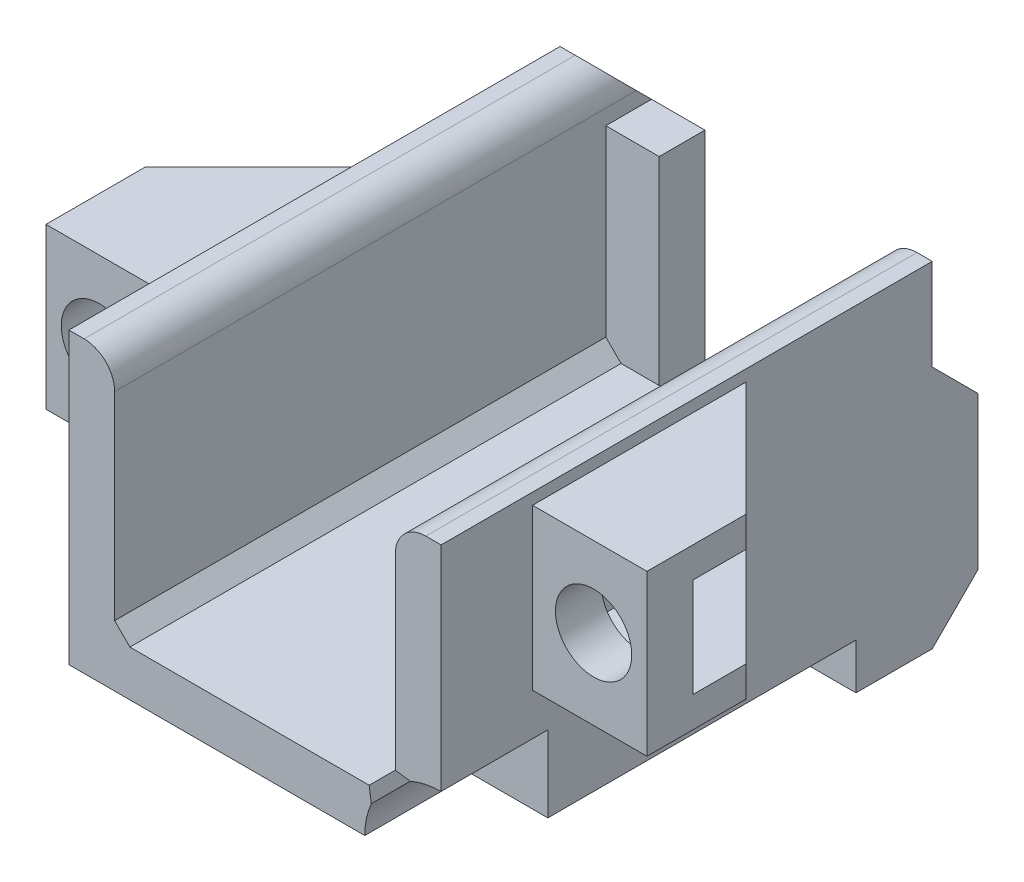
SolidWorks part; units mm, degrees
ref_plane "Front Plane" through (0, 0, 0) normal (0, 0, 1) x (1, 0, 0)
ref_plane "Top Plane" through (0, 0, 0) normal (0, 1, 0) x (1, 0, 0)
ref_plane "Right Plane" through (0, 0, 0) normal (1, 0, 0) x (0, 0, -1)
sketch "Sketch1" plane through (0, 0, 0) normal (0, 0, 1) x (1, 0, 0)
  line L0 (-9.2, 16) -> (-9.2, 0)
  line L1 (-9.2, 0) -> (9.2, 0)
  line L2 (9.2, 0) -> (9.2, 16)
  line L3 (-9.2, 16) -> (-12.2, 16)
  line L4 (-12.2, 16) -> (-12.2, -3)
  line L5 (-12.2, -3) -> (12.2, -3)
  line L6 (12.2, -3) -> (12.2, 16)
  line L7 (12.2, 16) -> (9.2, 16)
  dimension "D1" = 18.4
  dimension "D2" = 16
  dimension "D3" = 3
  dimension "D4" = 3
extrude "Boss-Extrude1" add sketch "Sketch1" along normal blind 32.2
sketch "Sketch2" plane through (0, 0, 32.2) normal (0, 0, 1) x (1, 0, 0)
  circle A0 centre (12.2, -3) radius 5
  point P2 (12.2, -3)
  dimension "D1" = 10
extrude "Cut-Extrude1" cut sketch "Sketch2" against normal blind 7
sketch "Sketch3" plane through (0, 0, 0) normal (0, 0, -1) x (-1, 0, 0)
  line L0 (9.2, 0) -> (9.2, 16) construction
  line L1 (-12.2, -3) -> (-2.2, -3)
  line L2 (-12.2, -3) -> (-12.2, 7)
  line L3 (-12.2, 7) -> (-2.2, 7)
  line L4 (-2.2, -3) -> (-2.2, 7)
  line L5 (12.2, -3) -> (5.7, -3)
  line L6 (12.2, -3) -> (12.2, 13)
  line L7 (12.2, 13) -> (5.7, 13)
  line L8 (5.7, -3) -> (5.7, 13)
  line L9 (-9.2, 16) -> (-9.2, 0) construction
  line L10 (-9.2, 0) -> (9.2, 0) construction
  dimension "D1" = 3.5
  dimension "D2" = 7
  dimension "D3" = 7
  dimension "D4" = 16
extrude "Boss-Extrude2" add sketch "Sketch3" along normal blind 3
sketch "Sketch4" plane through (0, -3, 0) normal (0, -1, 0) x (1, 0, 0)
  line L0 (-12.2, 32.2) -> (-12.2, -3) construction
  line L1 (-12.2, 0) -> (12.2, 0)
  line L2 (-12.2, 0) -> (-12.2, 5)
  line L3 (-12.2, 5) -> (12.2, 5)
  line L4 (12.2, 0) -> (12.2, 5)
  line L5 (12.2, 25.2) -> (12.2, -3) construction
  line L7 (-5.7, 0) -> (2.2, 0) construction
  dimension "D1" = 5
extrude "Boss-Extrude3" add sketch "Sketch4" along normal blind 3
sketch "Sketch5" plane through (0, 0, 0) normal (0, 0, 1) x (1, 0, 0)
  circle A0 centre (16.2, 10) radius 3.75 construction
  circle A1 centre (-16.2, 10) radius 3.75 construction
  circle A2 centre (16.2, 10) radius 3.75
  circle A3 centre (-16.2, 10) radius 3.75
sketch "Sketch6" plane through (12.2, 0, 0) normal (1, 0, 0) x (0, 0, -1)
  line L0 (0, 13.75) -> (0, 6.25) construction
  line L1 (0, 13.75) -> (0, 6.25) construction
  line L2 (0, 10) -> (-32.2, 10) construction
  line L3 (-32.2, 2) -> (-32.2, 16) construction
  line L4 (-22.2, 15.25) -> (-22.2, 13.25)
  line L5 (-26.2, 15.25) -> (-22.2, 15.25)
  line L6 (-26.2, 15.25) -> (-26.2, 4.75)
  line L7 (-26.2, 4.75) -> (-22.2, 4.75)
  line L8 (-22.2, 15.25) -> (-22.2, 4.75) construction
  line L9 (-22.2, 13.25) -> (-23.2, 13.25)
  line L10 (-23.2, 13.25) -> (-23.2, 6.75)
  line L11 (-23.2, 6.75) -> (-22.2, 6.75)
  line L12 (-22.2, 6.75) -> (-22.2, 4.75)
  point P10 (-26.2, 10)
  dimension "D1" = 6
  dimension "D2" = 6.5
  dimension "D3" = 2
  dimension "D4" = 3
  dimension "D5" = 1
extrude "Boss-Extrude4" add sketch "Sketch6" along normal blind 7.5
chamfer "Chamfer1" distance 10 angle 45 2 edges at (12.2, 5.75, 22.2) (12.2, 14.25, 22.2)
mirror "Mirror2" about plane through (0, 0, 0) normal (1, 0, 0) of "Boss-Extrude4"
chamfer "Chamfer2" distance 10 angle 45 2 edges at (-12.2, 5.75, 22.2) (-12.2, 14.25, 22.2)
sketch "Sketch7" plane through (0, 0, 23.2) normal (0, 0, -1) x (-1, 0, 0)
  circle A0 centre (-16.2, 10) radius 3.75 construction
  circle A1 centre (-16.2, 10) radius 3.75 construction
  circle A2 centre (-16.2, 10) radius 2.5
  dimension "D1" = 5
extrude "Cut-Extrude2" cut sketch "Sketch7" against normal blind 7.5
sketch "Sketch8" plane through (0, 0, 23.2) normal (0, 0, -1) x (-1, 0, 0)
  circle A0 centre (16.2, 10) radius 3.75 construction
  circle A1 centre (16.2, 10) radius 3.75 construction
  circle A2 centre (16.2, 10) radius 2.5
  dimension "D1" = 5
extrude "Cut-Extrude3" cut sketch "Sketch8" against normal blind 7.5
chamfer "Chamfer3" distance 1 angle 45 2 edges at (-9.2, 0, 16.1) (9.2, 0, 12.6)
chamfer "Chamfer4" distance 1 angle 45 2 edges at (9.2, 1, 28.7) (8.2, 0, 28.7) first distance on face at (10.6594, 1.6217, 28.7) first distance on face at (7.5783, -1.4594, 28.7)
fillet "Fillet1" radius 2 2 edges at (9.2, 16, 16.1) (-9.2, 16, 16.1)
chamfer "Chamfer5" distance 3 angle 45 2 edges at (-8.95, -3, 0) (7.2, -3, 0)
chamfer "Chamfer6" distance 3 angle 45 2 edges at (-10.7, 13, 0) (10.7, 7, 0)
